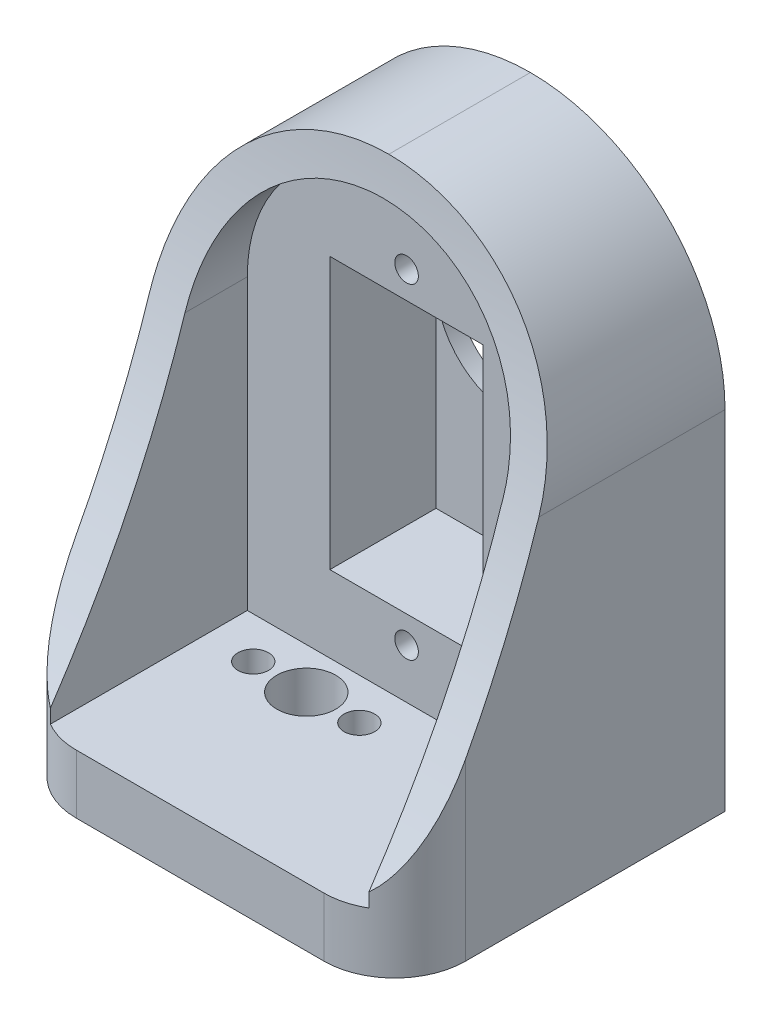
SolidWorks part; units mm, degrees
ref_plane "Front Plane" through (0, 0, 0) normal (0, 0, 1) x (1, 0, 0)
ref_plane "Top Plane" through (0, 0, 0) normal (0, 1, 0) x (1, 0, 0)
ref_plane "Right Plane" through (0, 0, 0) normal (1, 0, 0) x (0, 0, -1)
sketch "Sketch1" plane through (0, 0, 0) normal (0, 1, 0) x (1, 0, 0)
  line L1 (-16.5, 14) -> (16.5, 14)
  line L2 (-16.5, 14) -> (-16.5, -14)
  line L3 (-16.5, -14) -> (16.5, -14)
  line L4 (16.5, 14) -> (16.5, -14)
  line L5 (-16.5, 14) -> (16.5, -14) construction
  line L6 (-16.5, -14) -> (16.5, 14) construction
  point P0 (0, 0)
  dimension "D1" = 28
  dimension "D2" = 33
extrude "Boss-Extrude1" add sketch "Sketch1" along normal blind 46
sketch "Sketch2" plane through (16.5, 0, 0) normal (1, 0, 0) x (0, 0, -1)
  line L0 (-14, 0) -> (14, 0) construction
  line L1 (-14, 46) -> (3.5, 46)
  line L2 (-14, 46) -> (-14, 5)
  line L3 (-14, 5) -> (3.5, 5)
  line L4 (3.5, 46) -> (3.5, 5)
  line L5 (14, 46) -> (14, 0) construction
  dimension "D1" = 5
  dimension "D2" = 10.5
extrude "Cut-Extrude1" cut sketch "Sketch2" against normal through all
sketch "Sketch3" plane through (16.5, 0, 0) normal (1, 0, 0) x (0, 0, -1)
  line L0 (-14, 5) -> (3.5, 5) construction
  line L1 (3.5, 5) -> (3.5, 46) construction
  line L2 (-14, 5) -> (3.5, 5)
  line L3 (3.5, 5) -> (3.5, 46)
  line L4 (3.5, 46) -> (2, 46)
  spline S0 degree 2 poles (2, 46) (-1.1785, 23.4147) (-14, 5) knots 0 0 0 1 1 1
  point P5 (-8.3075, 16.4603)
  point P6 (-6.2319, 18.3473)
  dimension "D1" = 1.5
extrude "S" add sketch "Sketch3" against normal blind 3
mirror "Mirror1" about plane through (0, 0, 0) normal (1, 0, 0) of "S"
sketch "Sketch4" plane through (13.5, 0, 0) normal (-1, 0, 0) x (0, 0, 1)
  line L0 (-3.5, 43) -> (-1.5321, 43)
  line L3 (-2, 46) -> (-3.5, 46)
  line L4 (-3.5, 46) -> (-3.5, 5)
  line L5 (-3.5, 5) -> (14, 5)
  line L6 (-2, 46) -> (-3.5, 46)
  line L7 (-3.5, 46) -> (-3.5, 5)
  line L8 (-3.5, 5) -> (14, 5)
  parabola Q1 (14, 5) -> (-2, 46) focus (47.1049, 39.6514) apex (4.8554, 21.3784)
  parabola Q2 (14, 5) -> (-2, 46) focus (47.1049, 39.6514) apex (4.8554, 21.3784)
  spline M1 degree 2 poles (-2, 46) (1.1785, 23.4147) (14, 5) knots 0 0 0 1 1 1
  line M2 (-2, 46) -> (-3.5, 46)
  line M3 (-3.5, 46) -> (-3.5, 5)
  dimension "D2" = 3
  dimension "D1" = 0
extrude "Boss-Extrude3" add sketch "Sketch4" along normal up to surface (27 mm away) contours L0 M3 M1 M2 region at (13.5, 44.4322, -2.6316) up to face at (-13.5, 30.625, 1.4375)
fillet "Fillet1" radius 13.5 2 edges
fillet "Fillet2" radius 16.5 2 edges at (16.5, 46, -8) (-16.5, 46, -8)
fillet "Fillet3" radius 6 2 edges at (16.5, 2.5, 14) (-16.5, 2.5, 14)
sketch "Sketch5" plane through (0, 0, -3.5) normal (0, 0, 1) x (1, 0, 0)
  line L0 (-13.5, 5) -> (13.5, 5) construction
  line L1 (6.5, 34.5) -> (-6.5, 34.5)
  line L2 (6.5, 34.5) -> (6.5, 11.5)
  line L3 (6.5, 11.5) -> (-6.5, 11.5)
  line L4 (-6.5, 34.5) -> (-6.5, 11.5)
  line L5 (6.5, 34.5) -> (-6.5, 11.5) construction
  line L6 (6.5, 11.5) -> (-6.5, 34.5) construction
  point P0 (0, 23)
  point P7 (0, 11.5)
  dimension "D1" = 13
  dimension "D2" = 23
  dimension "D3" = 6.5
extrude "Cut-Extrude3" cut sketch "Sketch5" against normal blind 9
sketch "Sketch6" plane through (0, 0, -12.5) normal (0, 0, 1) x (1, 0, 0)
  line L0 (6.5, 34.5) -> (-6.5, 34.5) construction
  circle A0 centre (0, 28) radius 6.5
  point P2 (0, 24.9774)
  point P5 (0, 0)
  dimension "D1" = 13
  dimension "D2" = 6.5
extrude "Cut-Extrude4" cut sketch "Sketch6" against normal blind 9
sketch "Sketch7" plane through (0, 0, -3.5) normal (0, 0, 1) x (1, 0, 0)
  line L0 (0, 0) -> (0, 40.6056) construction
  line L1 (6.5, 34.5) -> (-6.5, 34.5) construction
  circle A0 centre (0, 36.8) radius 1
  circle A1 centre (0, 9.2) radius 1
  point P7 (0, 0)
  point P8 (0, 0)
  point P9 (0, 0)
  dimension "D1" = 2
  dimension "D2" = 2.3
  dimension "D3" = 27.6
extrude "Cut-Extrude5" cut sketch "Sketch7" against normal blind 8
sketch "Sketch8" plane through (0, 5, 0) normal (0, 1, 0) x (1, 0, 0)
  line L0 (-16.5, -1.7878) -> (-16.5, 14) construction
  circle A0 centre (-0.5, 0) radius 1.3
  circle A1 centre (-5, 0) radius 2.5
  circle A2 centre (-9.5, 0) radius 1.3
  dimension "D1" = 2.6
  dimension "D2" = 5
  dimension "D4" = 9
  dimension "D3" = 4.5
  dimension "D5" = 11.5
extrude "Cut-Extrude6" cut sketch "Sketch8" against normal through all
